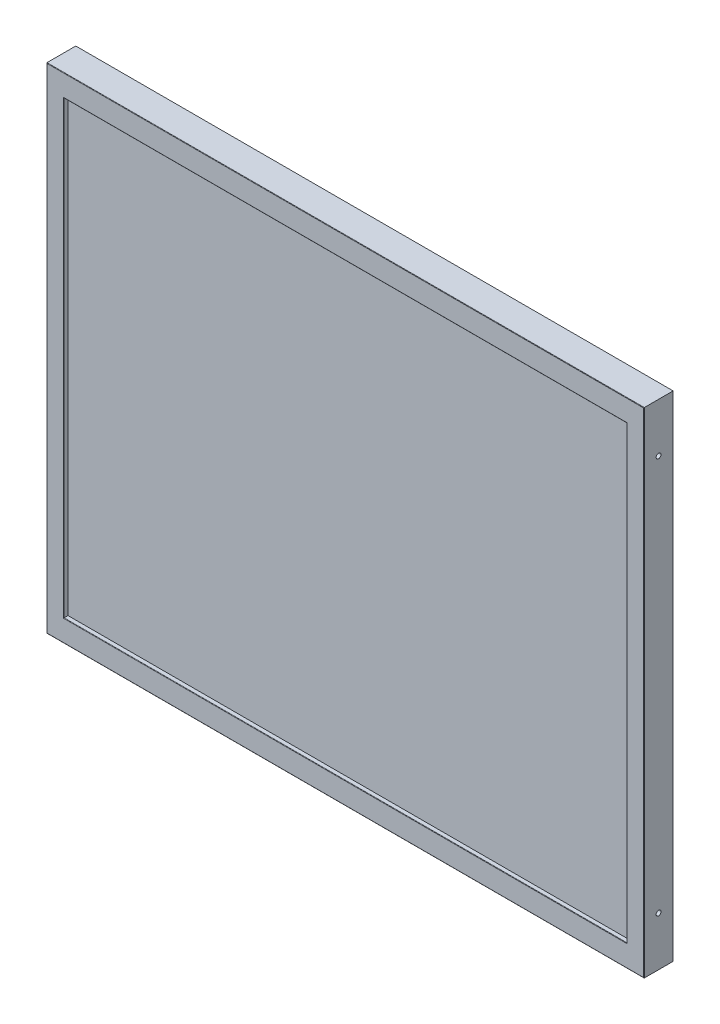
SolidWorks part; units mm, degrees
ref_plane "Front Plane" through (0, 0, 0) normal (0, 0, 1) x (1, 0, 0)
ref_plane "Top Plane" through (0, 0, 0) normal (0, 1, 0) x (1, 0, 0)
ref_plane "Right Plane" through (0, 0, 0) normal (1, 0, 0) x (0, 0, -1)
sketch "Sketch1" plane through (0, 0, 0) normal (0, 0, 1) x (1, 0, 0)
  line L1 (0, 0) -> (358.5, 0)
  line L2 (0, 0) -> (0, 296.5)
  line L3 (0, 296.5) -> (358.5, 296.5)
  line L4 (358.5, 0) -> (358.5, 296.5)
  dimension "D1" = 358.5
  dimension "D2" = 296.5
extrude "Boss-Extrude1" add sketch "Sketch1" along normal blind 17.5
sketch "Sketch2" plane through (0, 0, 17.5) normal (0, 0, 1) x (1, 0, 0)
  line L0 (0, 296.5) -> (0, 0) construction
  line L1 (10.3, 283.4) -> (348.2, 283.4)
  line L2 (10.3, 283.4) -> (10.3, 13.1)
  line L3 (10.3, 13.1) -> (348.2, 13.1)
  line L4 (348.2, 283.4) -> (348.2, 13.1)
  line L5 (358.5, 296.5) -> (0, 296.5) construction
  dimension "D1" = 337.9
  dimension "D2" = 270.3
  dimension "D3" = 10.3
  dimension "D4" = 13.1
extrude "Cut-Extrude1" cut sketch "Sketch2" against normal blind 2.54
fillet "Fillet1" radius 0.254 4 edges at (358.5, 148.25, 17.5) (179.25, 296.5, 17.5) (0, 148.25, 17.5) (179.25, 0, 17.5)
fillet "Fillet2" radius 0.254 4 edges at (348.2, 148.25, 14.96) (179.25, 13.1, 17.5) (10.3, 148.25, 17.5) (179.25, 283.4, 17.5)
sketch "Sketch3" plane through (0, 0, 0) normal (-1, 0, 0) x (0, 0, 1)
  line L0 (17.246, 296.5) -> (0, 296.5) construction
  line L1 (17.246, 0) -> (0, 0) construction
  line L4 (0, 296.5) -> (0, 0) construction
  circle A0 centre (8.75, 267.036) radius 1.4605
  circle A1 centre (8.75, 29.464) radius 1.4605
  dimension "D1" = 2.921
  dimension "D3" = 2.921
  dimension "D2" = 29.464
  dimension "D4" = 29.464
  dimension "D5" = 8.75
  dimension "D6" = 8.75
extrude "Cut-Extrude2" cut sketch "Sketch3" against normal blind 5.08
sketch "Sketch4" plane through (358.5, 0, 0) normal (1, 0, 0) x (0, 0, -1)
  line L0 (-17.246, 296.5) -> (0, 296.5) construction
  line L1 (0, 0) -> (0, 296.5) construction
  line L2 (-17.246, 0) -> (0, 0) construction
  circle A0 centre (-8.75, 267.036) radius 1.4605
  circle A1 centre (-8.75, 29.464) radius 1.4605
  dimension "D1" = 2.921
  dimension "D4" = 2.921
  dimension "D2" = 29.464
  dimension "D3" = 8.75
  dimension "D5" = 29.464
  dimension "D6" = 8.75
extrude "Cut-Extrude3" cut sketch "Sketch4" against normal blind 5.08
